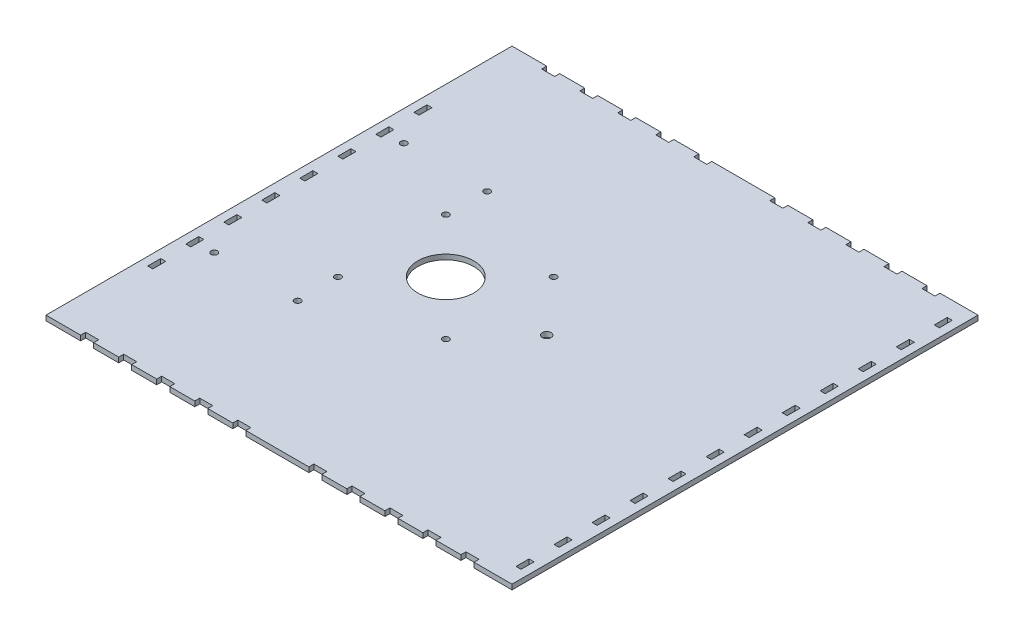
SolidWorks part; units mm, degrees
material "ENPH 253 Hardboard"
ref_plane "Front Plane" through (0, 0, 0) normal (0, 0, 1) x (1, 0, 0)
ref_plane "Top Plane" through (0, 0, 0) normal (0, 1, 0) x (1, 0, 0)
ref_plane "Right Plane" through (0, 0, 0) normal (1, 0, 0) x (0, 0, -1)
sketch "Sketch1" plane through (0, 0, 0) normal (0, 1, 0) x (1, 0, 0)
  line L0 (0, -139.7) -> (0, 139.7) construction
  line L1 (-139.7, 139.7) -> (139.7, 139.7)
  line L2 (-139.7, 139.7) -> (-139.7, -139.7)
  line L3 (-139.7, -139.7) -> (139.7, -139.7)
  line L4 (139.7, 139.7) -> (139.7, -139.7)
  line L5 (-139.7, 139.7) -> (139.7, -139.7) construction
  line L6 (-139.7, -139.7) -> (139.7, 139.7) construction
  line L12 (-139.7, 0) -> (139.7, 0) construction
  point P0 (0, 0)
  dimension "D1" = 279.4
  dimension "D2" = 279.4
extrude "Boss-Extrude1" add sketch "Sketch1" along normal blind 3
sketch "Sketch3" plane through (0, 0, 0) normal (0, -1, 0) x (-1, 0, 0)
  line L0 (-139.7, -139.7) -> (-139.7, 139.7) construction
  line L1 (-134.7, 129.3) -> (-131.7, 129.3)
  line L2 (-134.7, 129.3) -> (-134.7, 121.5)
  line L3 (-134.7, 121.5) -> (-131.7, 121.5)
  line L4 (-131.7, 129.3) -> (-131.7, 121.5)
  line L5 (-139.7, 139.7) -> (139.7, 139.7) construction
  dimension "D1" = 5
  dimension "D2" = 10.4
  dimension "D3" = 7.8
  dimension "D4" = 3
extrude "Cut-Extrude2" cut sketch "Sketch3" against normal through all
pattern_linear "LPattern1" count 12 spacing 22.8 along (0, 0, 1) of "Cut-Extrude2"
sketch "Sketch5" plane through (0, 0, 0) normal (0, -1, 0) x (1, 0, 0)
  line L0 (139.7, -139.7) -> (-139.7, -139.7) construction
  line L1 (109.1, -139.7) -> (116.9, -139.7)
  line L2 (109.1, -139.7) -> (109.1, -136.7)
  line L3 (109.1, -136.7) -> (116.9, -136.7)
  line L4 (116.9, -139.7) -> (116.9, -136.7)
  line L5 (139.7, 139.7) -> (139.7, -139.7) construction
  dimension "D1" = 22.8
  dimension "D2" = 7.8
  dimension "D3" = 3
extrude "Cut-Extrude3" cut sketch "Sketch5" against normal through all
pattern_linear "LPattern2" count 11 spacing 22.8 along (-1, 0, 0) skipping (5, 0) of "Cut-Extrude3"
mirror "Mirror2" about plane through (0, 0, 0) normal (0, 0, 1) of "LPattern2"
sketch "Sketch6" plane through (0, 0, 0) normal (0, -1, 0) x (1, 0, 0)
  line L0 (63.5, -139.7) -> (48.5, -139.7) construction
  line L1 (-134.7, -83.7) -> (-131.7, -83.7)
  line L2 (-134.7, -83.7) -> (-134.7, -75.9)
  line L3 (-134.7, -75.9) -> (-131.7, -75.9)
  line L4 (-131.7, -83.7) -> (-131.7, -75.9)
  line L5 (-139.7, -139.7) -> (-139.7, 139.7) construction
  dimension "D1" = 56
  dimension "D2" = 5
  dimension "D3" = 3
  dimension "D4" = 7.8
extrude "Cut-Extrude4" cut sketch "Sketch6" against normal through all
pattern_linear "LPattern3" count 8 spacing 22.8 along (0, 0, 1) of "Cut-Extrude4"
sketch "Sketch7" plane through (0, 0, 0) normal (0, -1, 0) x (-1, 0, 0)
  line L1 (139.7, 139.7) -> (139.7, -139.7) construction
  line L3 (-63.5, 139.7) -> (-48.5, 139.7) construction
  circle A0 centre (39.7, 0) radius 16.75
  dimension "D1" = 33.5
  dimension "D2" = 100
  dimension "D3" = 139.7
extrude "Cut-Extrude5" cut sketch "Sketch7" against normal through all
hole_wizard "#6 Clearance Hole1" positions "Sketch8" profile "Sketch9" hole size "#6" standard "ANSI Inch" end condition through all
sketch "Sketch8" plane through (0, 3, 0) normal (0, 1, 0) x (1, 0, 0)
  line L0 (-72.025, -32.325) -> (-72.025, 32.325) construction
  line L1 (-72.025, 32.325) -> (-7.375, 32.325) construction
  line L2 (-7.375, 32.325) -> (-7.375, -32.325) construction
  line L3 (-7.375, -32.325) -> (-72.025, -32.325) construction
  point P0 (-72.025, -32.325)
  point P2 (-72.025, 32.325)
  point P4 (-7.375, 32.325)
  point P6 (-7.375, -32.325)
  dimension "D1" = 64.65
  dimension "D2" = 64.65
  dimension "D3" = 90
  dimension "D4" = 64.65
  dimension "D5" = 32.325
  dimension "D6" = 32.325
sketch "Sketch9" plane through (-72.025, 3, 32.325) normal (1, 0, 0) x (0, 0, 1)
  line L0 (0, 0) -> (0, 3)
  line L1 (0, 3) -> (1.8986, 3)
  line L2 (1.8986, 3) -> (1.8986, 0)
  line L5 (1.8986, 0) -> (0, 0)
  line L11 (0, -6.35) -> (0, 107.95) construction
  dimension "Thru Hole Dia." = 3.7973
  dimension "Thru Hole Depth" = 3
hole_wizard "#6 Clearance Hole2" positions "Sketch10" profile "Sketch11" hole size "#6" standard "ANSI Inch" end condition through all
sketch "Sketch10" plane through (0, 3, 0) normal (0, 1, 0) x (1, 0, 0)
  line L0 (-139.7, 139.7) -> (-139.7, -139.7) construction
  line L1 (-118.9, 139.7) -> (-139.7, 139.7) construction
  line L2 (-139.7, -139.7) -> (-118.9, -139.7) construction
  line L3 (-73.3, 139.7) -> (-88.3, 139.7) construction
  line L4 (-88.3, -139.7) -> (-73.3, -139.7) construction
  point P0 (-121.7, 56.83)
  point P2 (-71.7, 56.83)
  point P4 (-121.7, -56.83)
  point P6 (-71.7, -56.83)
  point P9 (0, 0)
  point P12 (0, 0)
  point P13 (0, 0)
  dimension "D1" = 18
  dimension "D2" = 50
  dimension "D3" = 18
  dimension "D4" = 50
  dimension "D5" = 82.87
  dimension "D6" = 82.87
  dimension "D7" = 82.87
  dimension "D8" = 82.87
sketch "Sketch11" plane through (-121.7, 3, -56.83) normal (1, 0, 0) x (0, 0, 1)
  line L0 (0, 0) -> (0, 3)
  line L1 (0, 3) -> (1.8986, 3)
  line L2 (1.8986, 3) -> (1.8986, 0)
  line L5 (1.8986, 0) -> (0, 0)
  line L11 (0, -6.35) -> (0, 107.95) construction
  dimension "Thru Hole Dia." = 3.7973
  dimension "Thru Hole Depth" = 3
sketch "Sketch14" plane through (0, 0, 0) normal (0, -1, 0) x (-1, 0, 0)
  line L0 (139.7, 139.7) -> (139.7, -139.7) construction
  line L1 (-17.9, 139.7) -> (19.9, 139.7) construction
  circle A0 centre (-20.8, 0) radius 2.65
  dimension "D1" = 5.3
  dimension "D2" = 160.5
  dimension "D3" = 139.7
extrude "Cut-Extrude6" cut sketch "Sketch14" against normal through all
